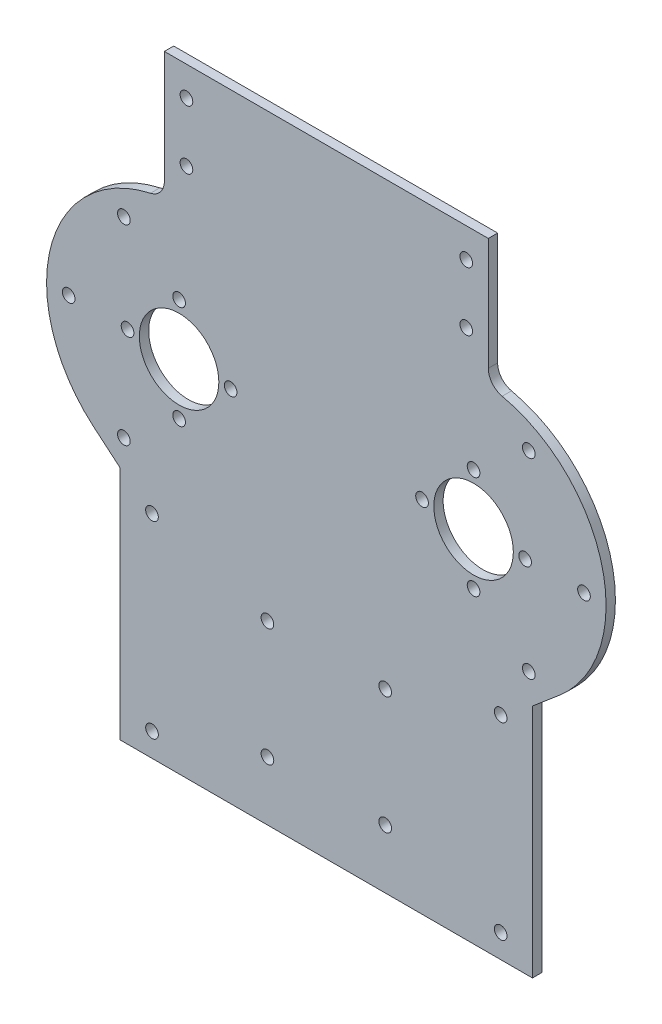
SolidWorks part; units mm, degrees
ref_plane "Front Plane" through (0, 0, 0) normal (0, 0, 1) x (1, 0, 0)
ref_plane "Top Plane" through (0, 0, 0) normal (0, 1, 0) x (1, 0, 0)
ref_plane "Right Plane" through (0, 0, 0) normal (1, 0, 0) x (0, 0, -1)
sketch "Sketch1" plane through (0, 0, 0) normal (0, 0, 1) x (1, 0, 0)
  line L1 (-100, -75) -> (100, -75)
  line L2 (-100, -75) -> (-100, 75)
  line L3 (-100, 75) -> (100, 75)
  line L4 (100, -75) -> (100, 75)
  line L5 (-100, -75) -> (100, 75) construction
  line L6 (-100, 75) -> (100, -75) construction
  line L8 (-47.5, 40) -> (47.5, 40) construction
  line L9 (0, 75) -> (0, -75) construction
  line L10 (-27, -44) -> (27, -44) construction
  line L11 (-27, -44) -> (-27, 28) construction
  line L12 (-27, 28) -> (27, 28) construction
  line L13 (27, -44) -> (27, 28) construction
  line L14 (-27, -44) -> (27, 28) construction
  line L15 (-27, 28) -> (27, -44) construction
  line L23 (-55, 70) -> (55, 70)
  line L24 (-55, 70) -> (-55, -70)
  line L25 (-55, -70) -> (55, -70)
  line L26 (55, 70) -> (55, -70)
  line L27 (-55, 70) -> (55, -70) construction
  line L28 (-55, -70) -> (55, 70) construction
  line L29 (-32.5, 70) -> (32.5, 70) construction
  line L30 (-32.5, 70) -> (-32.5, 55) construction
  line L31 (-32.5, 55) -> (32.5, 55) construction
  line L32 (32.5, 70) -> (32.5, 55) construction
  line L33 (-32.5, 70) -> (32.5, 55) construction
  line L34 (-32.5, 55) -> (32.5, 70) construction
  circle A2 centre (-47.5, 40) radius 2.15
  circle A3 centre (47.5, 40) radius 2.15
  circle A4 centre (-27, 28) radius 2 construction
  circle A5 centre (27, 28) radius 2 construction
  circle A6 centre (27, -44) radius 2 construction
  circle A7 centre (-27, -44) radius 2 construction
  circle A8 centre (-47.5, 60) radius 2.15
  circle A10 centre (47.5, 60) radius 2.15
  point P0 (0, 0)
  point P15 (0, 40)
  point P18 (0, -8)
  point P56 (0, 0)
  point P63 (0, 62.5)
  dimension "D3" = 4.3
  dimension "D4" = 20
  dimension "D5" = 4.3
  dimension "D8" = 4
  dimension "D1" = 150
  dimension "D2" = 200
  dimension "D6" = 72
  dimension "D7" = 54
  dimension "D14" = 30
  dimension "D15" = 140
  dimension "D16" = 110
  dimension "D17" = 95
  dimension "D18" = 12
  dimension "D19" = 15
  dimension "D20" = 65
extrude "Boss-Extrude1" add sketch "Sketch1" along normal blind 3.175 contours L23 L32 L31 L30 L24 L25 L26 A7 A6 A5 A4 A3 A2 region at (0, -0.1893, 0)
sketch "Sketch3" plane through (0, 0, 3.175) normal (0, 0, 1) x (1, 0, 0)
  line L0 (0, 31.3301) -> (0, 52.1198) construction
  line L1 (-50, -18) -> (-68.75, 14.476) construction
  line L2 (-50, -18) -> (50, -18) construction
  line L3 (-50, -18) -> (-87.5, -18) construction
  line L4 (-50, -18) -> (-68.75, 14.476) construction
  circle A0 centre (-50, -18) radius 45
  circle A1 centre (-50, -0.5) radius 2.15
  circle A2 centre (50, -18) radius 45
  circle A3 centre (-50, -18) radius 30
  circle A4 centre (50, -18) radius 30
  circle A5 centre (-47.5, 40) radius 2.15 construction
  circle A6 centre (-47.5, 40) radius 2
  circle A7 centre (47.5, 40) radius 2
  circle A8 centre (-32.5, -18) radius 2.15
  circle A9 centre (-50, -35.5) radius 2.15
  circle A10 centre (-67.5, -18) radius 2.15
  circle A11 centre (67.5, -18) radius 2.15
  circle A12 centre (50, -35.5) radius 2.15
  circle A13 centre (32.5, -18) radius 2.15
  circle A14 centre (50, -0.5) radius 2.15
  circle A15 centre (-50, -18) radius 13.5
  circle A16 centre (50, -18) radius 13.5
  circle A18 centre (-68.75, 14.476) radius 2.15
  circle A19 centre (-50, -18) radius 37.5 construction
  circle A21 centre (68.75, 14.476) radius 2.15
  circle A22 centre (-87.5, -18) radius 2.15
  circle A23 centre (-68.75, -50.476) radius 2.15
  circle A24 centre (68.75, -50.476) radius 2.15
  circle A25 centre (87.5, -18) radius 2.15
  circle A26 centre (68.75, 14.476) radius 2.15
  point P28 (-50, -18)
  line M4 (55, -70) -> (55, 70)
  line M6 (-55, 70) -> (-55, -70)
  line M12 (-55, -70) -> (55, -70)
  circle M17 centre (-47.5, 40) radius 2.15
  circle M18 centre (47.5, 40) radius 2.15
  dimension "D1" = 100
  dimension "D2" = 90
  dimension "D3" = 58
  dimension "D4" = 60
  dimension "D5" = 4.3
  dimension "D7" = 35
  dimension "D8" = 27
  dimension "D9" = 7.5
  dimension "D10" = 4.3
  dimension "D13" = 4.3
  dimension "D6" = 4
  dimension "D11" = 60
  dimension "D12" = 60
extrude "Boss-Extrude3" add sketch "Sketch3" against normal up to surface (3.175 mm away) contours A3 M6 | A3 A0 M6 | A3 A0 M12 M6 M17 | A3 M6 | A4 M4 | A4 M4 | A4 A2 M4 | A4 A2 M4 M12 M18 region at (-20.6864, -50.7736, 3.175) region at (6.0296, -18, 3.175) region at (55.9798, -55.1509, 3.175) region at (-55.9798, 19.1509, 3.175) region at (-55.6423, 3.0602, 3.175) region at (-31.0835, 4.3824, 3.175) region at (55.6423, -39.0602, 3.175) region at (20.6946, -18, 3.175) up to face at (0, 0, 0)
sketch "Sketch4" plane through (0, 0, 3.175) normal (0, 0, 1) x (1, 0, 0)
  line L0 (-70, -95) -> (-60, -95) construction
  line L1 (-60, -60) -> (-66.1555, -60)
  line L2 (-60, -60) -> (-60, -130)
  line L3 (-60, -130) -> (-115, -130)
  line L4 (-70, -60) -> (-70, -130)
  line L5 (-60, -60) -> (-70, -130) construction
  line L6 (-60, -130) -> (-70, -60) construction
  line L11 (-70, -60) -> (-79.0124, -52.3989)
  line L12 (-66.1555, -60) -> (-70, -60)
  line L13 (-60, -130) -> (-115, -130) construction
  line L14 (-60, -130) -> (-60, -121.7157)
  line L19 (-115, -130) -> (-70, -130)
  line L21 (-60, -95) -> (-60, -60) construction
  line L28 (-60, -60) -> (0, -60)
  line L29 (-60, -60) -> (-60, -130)
  line L30 (-60, -130) -> (0, -130)
  line L31 (0, -60) -> (0, -130)
  line L32 (-60, -60) -> (0, -130) construction
  line L33 (-60, -130) -> (0, -60) construction
  line L34 (-70, -130) -> (0, -130)
  line L35 (-70, -130) -> (-70, -140)
  line L36 (-70, -140) -> (0, -140)
  line L37 (0, -130) -> (0, -140)
  line L38 (-70, -130) -> (0, -140) construction
  line L39 (-70, -140) -> (0, -130) construction
  arc A0 (-55, 26.7214) -> (-55, -62.7214) centre (-50, -18) ccw construction
  arc A1 (-79.0124, -52.3989) -> (-66.1555, -60) centre (-50, -18) ccw
  circle A2 centre (-60, -65) radius 2.05 construction
  point P4 (-65, -95)
  point P12 (-35, -135)
  point P26 (-30, -95)
  arc M12 (-55, 26.7214) -> (-55, -62.7214) centre (-50, -18) ccw
  line M18 (-55, -70) -> (55, -70)
  line M85 (-55, -62.7214) -> (-55, -70)
  dimension "D7" = 4.1
  dimension "D1" = 60
  dimension "D2" = 60
  dimension "D3" = 70
  dimension "D4" = 10
  dimension "D5" = 10
  dimension "D6" = 10
  dimension "D10" = 5
extrude "Boss-Extrude5" add sketch "Sketch4" against normal up to surface (3.175 mm away) contours L12 L4 M12 | L12 L11 M12 | L31 L2 L30 M18 M85 M12 | L29 L28 L31 L30 | L35 L34 L37 L36 region at (-65.0259, -95.3101, 3.175) region at (-70.9896, -58.2464, 3.175) region at (-30.2897, -99.6442, 3.175) up to face at (59.25, -18, 0)
mirror "Mirror2" about plane through (0, 0, 0) normal (1, 0, 0) of "Boss-Extrude5"
fillet "Fillet1" radius 6 2 edges at (55, 26.7214, 1.5875) (-55, 26.7214, 1.5875)
ref_plane "Plane1" through (-55, -5.4601, 3.175) normal (0, -1, 0) x (-1, 0, 0)
sketch "Sketch6" plane through (0, 0, 3.175) normal (0, 0, 1) x (1, 0, 0)
  circle A0 centre (32.5, -18) radius 2.15 construction
  circle A1 centre (50, -0.5) radius 2.15 construction
  circle A2 centre (67.5, -18) radius 2.15 construction
  circle A3 centre (50, -18) radius 13.5 construction
  circle A4 centre (50, -35.5) radius 2.15 construction
  circle A5 centre (-50, -18) radius 13.5 construction
  circle A6 centre (-67.5, -18) radius 2.15 construction
  circle A7 centre (-50, -35.5) radius 2.15 construction
  circle A8 centre (-32.5, -18) radius 2.15 construction
  circle A9 centre (-50, -0.5) radius 2.15 construction
  circle A10 centre (32.5, -18) radius 2.15
  circle A11 centre (50, -0.5) radius 2.15
  circle A12 centre (67.5, -18) radius 2.15
  circle A13 centre (50, -18) radius 13.5
  circle A14 centre (50, -35.5) radius 2.15
  circle A15 centre (-50, -18) radius 13.5
  circle A16 centre (-67.5, -18) radius 2.15
  circle A17 centre (-50, -35.5) radius 2.15
  circle A18 centre (-32.5, -18) radius 2.15
  circle A19 centre (-50, -0.5) radius 2.15
extrude "Cut-Extrude1" cut sketch "Sketch6" against normal blind 10
sketch "Sketch7" plane through (0, 0, 3.175) normal (0, 0, 1) x (1, 0, 0)
  line L0 (-70, -60) -> (70, -60) construction
  line L1 (-70, -100) -> (70, -100) construction
  line L2 (-70, -76) -> (-50, -76) construction
  line L3 (-70, -76) -> (-70, -60) construction
  line L4 (-70, -60) -> (-50, -60) construction
  line L5 (-50, -76) -> (-50, -60) construction
  line L6 (-70, -76) -> (-50, -60) construction
  line L7 (-70, -60) -> (-50, -76) construction
  line L8 (-70, -60) -> (-70, -140) construction
  line L9 (70, -60) -> (70, -140) construction
  line L10 (0, -140) -> (0, -60) construction
  line L11 (-70, -140) -> (70, -140) construction
  circle A5 centre (-59.2, -68) radius 2.15
  circle A6 centre (-59.2, -132) radius 2.15
  circle A7 centre (59.2, -132) radius 2.15
  circle A8 centre (59.2, -68) radius 2.15
  point P6 (-60, -68)
  dimension "D1" = 16
  dimension "D3" = 4.3
  dimension "D2" = 20
  dimension "D4" = 10.8
  dimension "D5" = 8
extrude "Cut-Extrude2" cut sketch "Sketch7" against normal through all
sketch "Sketch8" plane through (0, 0, 3.175) normal (0, 0, 1) x (1, 0, 0)
  line L0 (0, -140) -> (0, -37.937) construction
  line L1 (-70, -140) -> (70, -140) construction
  line L2 (-54.7469, -100) -> (38.076, -100) construction
  circle A0 centre (-20, -120) radius 2.15
  circle A1 centre (20, -120) radius 2.15
  circle A2 centre (20, -80) radius 2.15
  circle A3 centre (-20, -80) radius 2.15
  dimension "D1" = 4.3
  dimension "D2" = 20
  dimension "D3" = 20
extrude "Cut-Extrude3" cut sketch "Sketch8" against normal through all
